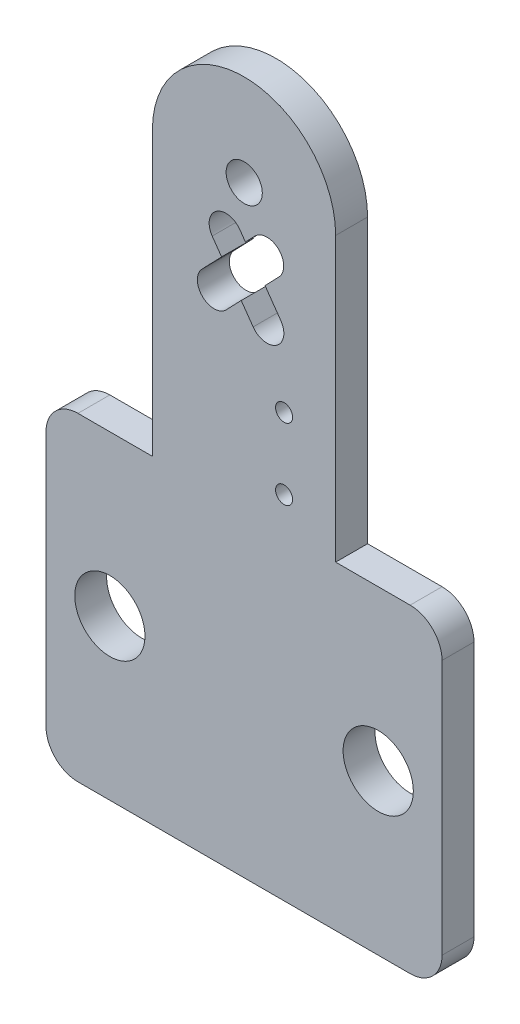
SolidWorks part; units mm, degrees
ref_plane "Front Plane" through (0, 0, 0) normal (0, 0, 1) x (1, 0, 0)
ref_plane "Top Plane" through (0, 0, 0) normal (0, 1, 0) x (1, 0, 0)
ref_plane "Right Plane" through (0, 0, 0) normal (1, 0, 0) x (0, 0, -1)
sketch "Sketch1" plane through (0, 0, 0) normal (0, 0, 1) x (1, 0, 0)
  line L5 (50.7738, 15) -> (50.7738, 41.5958)
  line L6 (50.7738, 15) -> (40.7738, 15)
  line L7 (78, -15) -> (40.7738, -15)
  line L9 (78, -15) -> (78, 15)
  line L13 (68, 15) -> (68, 41.5958)
  line L14 (78, 15) -> (68, 15)
  line L15 (40.7738, -15) -> (40.7738, 15)
  arc A0 (68, 41.5958) -> (50.7738, 41.5958) centre (59.3869, 41.5958) ccw
  point P2 (59.3869, 0)
extrude "Boss-Extrude1" add sketch "Sketch1" along normal blind 3
hole_wizard "M3 Clearance Hole1" positions "Sketch2" profile "Sketch3" hole size "M3" standard "ISO" end condition through all
sketch "Sketch2" plane through (0, 0, 3) normal (0, 0, 1) x (1, 0, 0)
  point P0 (59.4035, 41.5958)
sketch "Sketch3" plane through (59.4035, 41.5958, 3) normal (1, 0, 0) x (0, -1, 0)
  line L0 (0, 0) -> (0, 3)
  line L1 (0, 3) -> (1.7, 3)
  line L2 (1.7, 3) -> (1.7, 0)
  line L5 (1.7, 0) -> (0, 0)
  line L11 (0, -6.35) -> (0, 107.95) construction
  dimension "Thru Hole Dia." = 3.4
  dimension "Thru Hole Depth" = 3
hole_wizard "M6 Clearance Hole1" positions "Sketch4" profile "Sketch5" hole size "M6" standard "ISO" end condition through all
sketch "Sketch4" plane through (0, 0, 3) normal (0, 0, 1) x (1, 0, 0)
  line L1 (40.7738, 15) -> (40.7738, -15) construction
  line L2 (78, -15) -> (78, 15) construction
  line L3 (59.1771, -15) -> (59.1771, 15) construction
  line L4 (40.7738, -15) -> (78, -15) construction
  line L5 (59.1771, 15) -> (50.7738, 15) construction
  point P0 (46.7738, 0)
  point P4 (72, 0)
  dimension "D1" = 6
  dimension "D2" = 6
sketch "Sketch5" plane through (46.7738, 0, 3) normal (1, 0, 0) x (0, -1, 0)
  line L0 (0, 0) -> (0, 3)
  line L1 (0, 3) -> (3.3, 3)
  line L2 (3.3, 3) -> (3.3, 0)
  line L5 (3.3, 0) -> (0, 0)
  line L11 (0, -6.35) -> (0, 107.95) construction
  dimension "Thru Hole Dia." = 6.6
  dimension "Thru Hole Depth" = 3
fillet "Fillet1" radius 3 4 edges at (78, -15, 1.5) (40.7738, -15, 1.5) (40.7738, 15, 1.5) (78, 15, 1.5)
sketch "Sketch6" plane through (0, 0, 0) normal (0, 0, -1) x (-1, 0, 0)
  line L0 (-50.7738, 15) -> (-68, 15) construction
  line L1 (-59.121, 31.8633) -> (-60.2422, 30.2687)
  line L2 (-58.9921, 37.5667) -> (-59.5167, 36.8206)
  line L4 (-62.6763, 35.5621) -> (-61.3626, 34.1953)
  line L5 (-56.3948, 35.7405) -> (-57.2751, 34.4886)
  line L11 (-59.121, 31.8633) -> (-57.7117, 30.397)
  line L12 (-55.4406, 32.58) -> (-57.2751, 34.4886)
  line L14 (-59.5167, 36.8206) -> (-60.4052, 37.7451)
  line L15 (-61.3626, 34.1953) -> (-62.8394, 32.0949)
  arc A1 (-56.3948, 35.7405) -> (-58.9921, 37.5667) centre (-57.6935, 36.6536) ccw
  arc A2 (-62.8394, 32.0949) -> (-60.2422, 30.2687) centre (-61.5408, 31.1818) ccw
  arc A4 (-60.4052, 37.7451) -> (-62.6763, 35.5621) centre (-61.5408, 36.6536) ccw
  arc A5 (-57.7117, 30.397) -> (-55.4406, 32.58) centre (-56.5761, 31.4885) ccw
  point P13 (-59.6171, 33.9177)
  point P18 (-60.4638, 35.5422)
  point P20 (-59.0585, 34.071)
extrude "Cut-Extrude1" cut sketch "Sketch6" against normal blind 10 contours A2 L5 A1 region at (59.3349, 33.9245, 0)
hole_wizard "Tap Drill for M2 Tap1" positions "Sketch7" profile "Sketch8" hole size "M2" standard "ISO" end condition through all
sketch "Sketch7" plane through (0, 0, 3) normal (0, 0, 1) x (1, 0, 0)
  point P0 (63.15, 24.765)
  point P3 (63.15, 18.065)
sketch "Sketch8" plane through (63.15, 24.765, 3) normal (1, 0, 0) x (0, -1, 0)
  line L0 (0, 0) -> (0, 3)
  line L1 (0, 3) -> (0.8, 3)
  line L2 (0.8, 3) -> (0.8, 0)
  line L5 (0.8, 0) -> (0, 0)
  line L11 (0, -6.35) -> (0, 107.95) construction
  dimension "Thru Hole Dia." = 1.6
  dimension "Thru Hole Depth" = 3
equation "\"D2@Sketch4\"=\"D1@Sketch4\""
